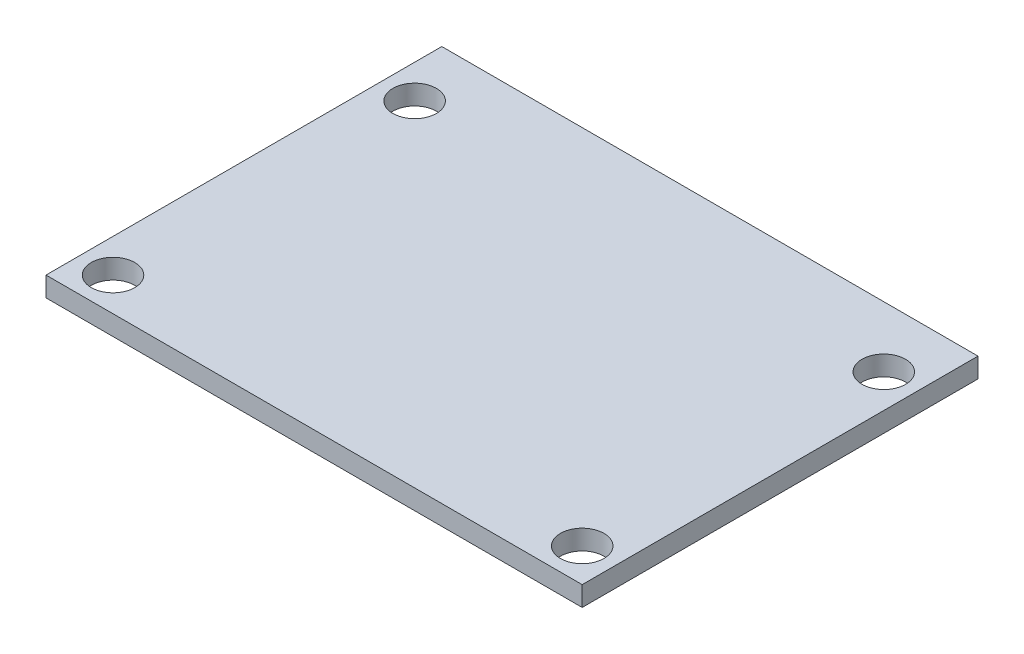
SolidWorks part; units mm, degrees
ref_plane "Płaszczyzna przednia" through (0, 0, 0) normal (0, 0, 1) x (1, 0, 0)
ref_plane "Płaszczyzna górna" through (0, 0, 0) normal (0, 1, 0) x (1, 0, 0)
ref_plane "Płaszczyzna prawa" through (0, 0, 0) normal (1, 0, 0) x (0, 0, -1)
sketch "Szkic2" plane through (0, 0, 0) normal (0, 1, 0) x (1, 0, 0)
  line L0 (0, -15) -> (0, 15) construction
  line L1 (20.32, -15) -> (-20.32, -15)
  line L2 (20.32, -15) -> (20.32, 15)
  line L3 (20.32, 15) -> (-20.32, 15)
  line L4 (-20.32, -15) -> (-20.32, 15)
  line L5 (20.32, -15) -> (-20.32, 15) construction
  line L6 (20.32, 15) -> (-20.32, -15) construction
  circle A0 centre (-17.78, -12.46) radius 1.65
  circle A1 centre (-17.78, 10.4) radius 1.65
  circle A2 centre (17.78, -12.46) radius 1.65
  circle A3 centre (17.78, 10.4) radius 1.65
  point P0 (0, 0)
  dimension "D3" = 2.54
  dimension "D5" = 3.3
  dimension "D7" = 22.86
  dimension "D8" = 35.56
  dimension "D1" = 40.64
  dimension "D2" = 30
  dimension "D4" = 2.54
  dimension "D6" = 2
extrude "Dodanie-wyciągnięcie1" add sketch "Szkic2" along normal blind 1.5
